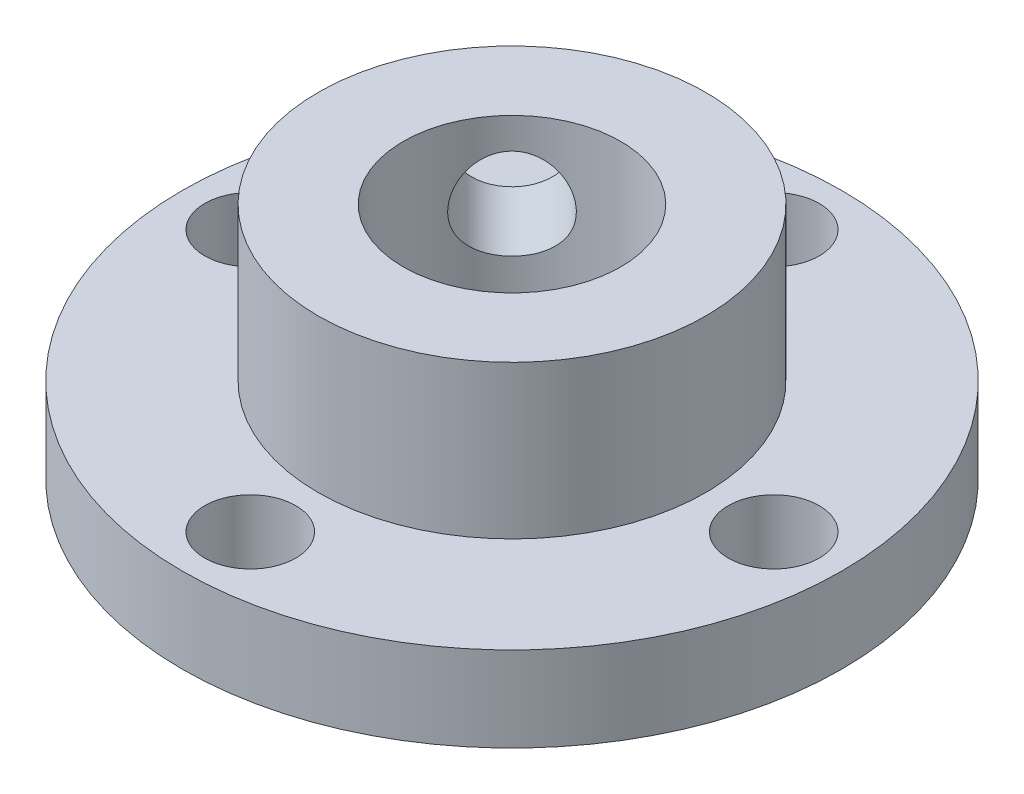
SolidWorks part; units mm, degrees
ref_plane "Front Plane" through (0, 0, 0) normal (0, 0, 1) x (1, 0, 0)
ref_plane "Top Plane" through (0, 0, 0) normal (0, 1, 0) x (1, 0, 0)
ref_plane "Right Plane" through (0, 0, 0) normal (1, 0, 0) x (0, 0, -1)
sketch "Sketch1" plane through (0, 0, 0) normal (0, 1, 0) x (1, 0, 0)
  circle A0 centre (0, 0) radius 4.064
  circle A1 centre (0, 0) radius 7.239
  circle A2 centre (0, 0) radius 12.319
  dimension "D1" = 8.128
  dimension "D2" = 3.175
  dimension "D3" = 5.08
extrude "Boss-Extrude1" add sketch "Sketch1" along normal blind 8.89 contours A1 A0 region at (-7.0343, 0, 0)
extrude "Boss-Extrude2" add sketch "Sketch1<3>" along normal blind 3.175 contours A2 A1 region at (-11.9706, 0, 0)
sketch "Sketch1<3>" plane through (0, 0, 0) normal (0, 1, 0) x (1, 0, 0) same geometry as "Sketch1"
sketch "Sketch2" plane through (0, 3.175, 0) normal (0, 1, 0) x (1, 0, 0)
  line L0 (0, 12.319) -> (0, 7.239) construction
  circle A0 centre (0, 9.779) radius 1.7
  circle A1 centre (9.779, 0) radius 1.7
  circle A2 centre (0, -9.779) radius 1.7
  circle A3 centre (-9.779, 0) radius 1.7
  circle A4 centre (0, 0) radius 12.319 construction
  circle A5 centre (0, 0) radius 7.239 construction
  point P2 (0, 0)
  point P3 (0, 14.692)
  point P4 (0, 9.779)
  point P11 (0, 0)
  dimension "D1" = 3.4
  dimension "D2" = 4
extrude "Cut-Extrude1" cut sketch "Sketch2" against normal blind 3.175
ref_axis "Axis1" through (0, 0, -9.779) along (0, 1, 0)
ref_axis "Axis2" through (-9.779, 0, 0) along (0, 1, 0)
ref_plane "Plane1" through (-4.8895, 0, -4.8895) normal (-0.7071, 0, -0.7071) x (-0.7071, 0, 0.7071)
sketch "Sketch5" plane through (-4.8895, 0, -4.8895) normal (-0.7071, 0, -0.7071) x (-0.7071, 0, 0.7071)
  line L0 (0, 8.89) -> (0, 3.175) construction
  line L1 (7.239, 8.89) -> (-7.239, 8.89) construction
  line L2 (12.319, 3.175) -> (-12.319, 3.175) construction
  circle A0 centre (0, 6.0325) radius 1.7
  point P9 (0, 12.1325)
  point P10 (0, 6.0325)
  dimension "D1" = 3.4
extrude "Cut-Extrude2" cut sketch "Sketch5" against normal up to next and the other way up to next
sketch "Sketch6" plane through (0, 0, 0) normal (0, 1, 0) x (1, 0, 0)
  circle A0 centre (0, 0) radius 9.779 construction
